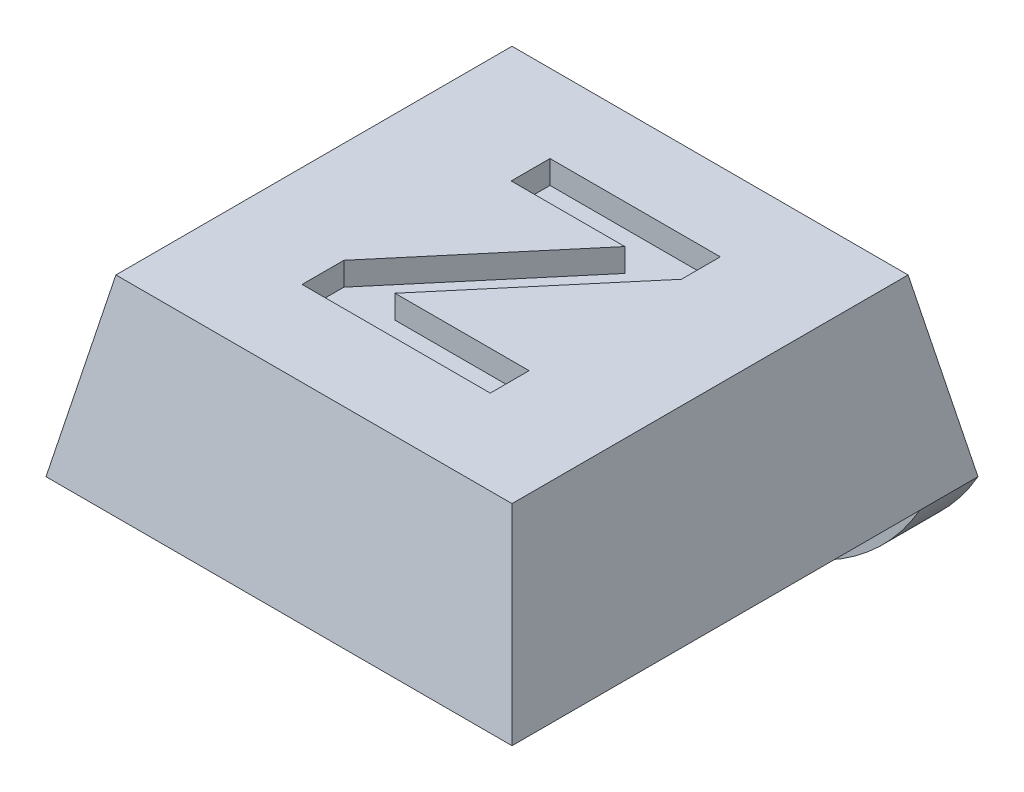
SolidWorks part; units mm, degrees
ref_plane "Front Plane" through (0, 0, 0) normal (0, 0, 1) x (1, 0, 0)
ref_plane "Top Plane" through (0, 0, 0) normal (0, 1, 0) x (1, 0, 0)
ref_plane "Right Plane" through (0, 0, 0) normal (1, 0, 0) x (0, 0, -1)
sketch "Sketch1" plane through (0, 0, 0) normal (0, 1, 0) x (1, 0, 0)
  line L1 (0, 0) -> (8, 0)
  line L2 (0, 0) -> (0, 8)
  line L3 (0, 8) -> (8, 8)
  line L4 (8, 0) -> (8, 8)
  dimension "D1" = 8
  dimension "D2" = 8
extrude "Boss-Extrude1" add sketch "Sketch1" along normal blind 3
sketch "Sketch2" plane through (0, 0, 0) normal (0, 0, 1) x (1, 0, 0)
  line L0 (0, 0) -> (0.6, 3)
  line L1 (0, 3) -> (8, 3) construction
  line L2 (0.6, 3) -> (0, 3)
  line L3 (0, 3) -> (0, 0)
  line L4 (8, 0) -> (7.4, 3)
  line L5 (7.4, 3) -> (8, 3)
  line L6 (8, 3) -> (8, 0)
  dimension "D1" = 0.6
  dimension "D2" = 0.6
extrude "Cut-Extrude1" cut sketch "Sketch2" against normal through all both and the other way through all
sketch "Sketch3" plane through (0, 0, 0) normal (1, 0, 0) x (0, 0, -1)
  line L0 (0, 0) -> (0.6, 3)
  line L1 (8, 3) -> (0, 3) construction
  line L2 (0.6, 3) -> (0, 3)
  line L3 (0, 3) -> (0, 0)
  line L4 (8, 3) -> (7.4, 3)
  line L5 (7.4, 3) -> (8, 0)
  line L6 (8, 3) -> (8, 0)
  dimension "D1" = 0.6
  dimension "D2" = 0.6
extrude "Cut-Extrude2" cut sketch "Sketch3" along normal blind 11
sketch "Sketch4" plane through (0, 0, 0) normal (0, -1, 0) x (1, 0, 0)
  line L0 (8, 0) -> (8, -8) construction
  line L3 (0, 0) -> (8, 0) construction
  circle A0 centre (4, -3.75) radius 1.75
  dimension "D1" = 3.5
  dimension "D2" = 4
  dimension "D3" = 3.75
extrude "Cut-Extrude3" cut sketch "Sketch4" against normal blind 0.4
sketch "Sketch5" plane through (0, 0, 0) normal (0, -1, 0) x (1, 0, 0)
  line L0 (8, 0) -> (8, -8) construction
  line L1 (0, -8) -> (8, -8)
  line L2 (0, -8) -> (0, -7)
  line L3 (0, -7) -> (8, -7)
  line L4 (8, -8) -> (8, -7)
  dimension "D1" = 1
extrude "Boss-Extrude2" add sketch "Sketch5" along normal blind 2
fillet "Fillet1" radius 4 2 edges at (8, -2, -7.5) (0, -2, -7.5)
sketch "Sketch6" plane through (0, 3, 0) normal (0, 1, 0) x (1, 0, 0)
  text T0 "Z" font "Arial" height 4
extrude "Cut-Extrude4" cut sketch "Sketch6" against normal blind 0.4
